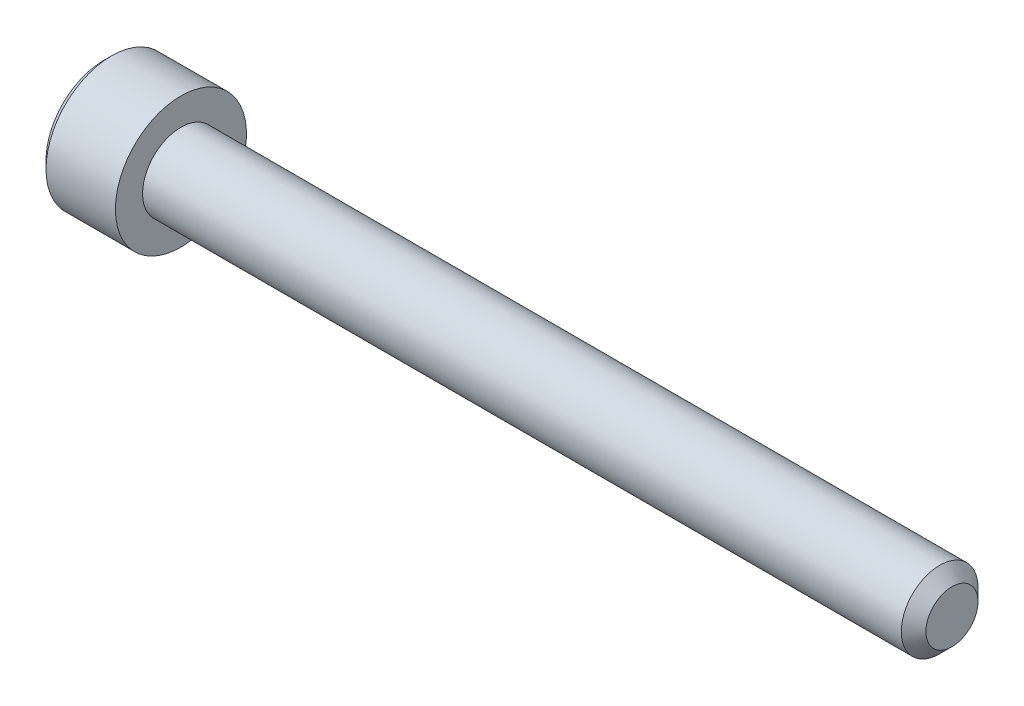
SolidWorks part; units mm, degrees
material "AISI Type 316L stainless steel"
ref_plane "Front Plane" through (0, 0, 0) normal (0, 0, 1) x (1, 0, 0)
ref_plane "Top Plane" through (0, 0, 0) normal (0, 1, 0) x (1, 0, 0)
ref_plane "Right Plane" through (0, 0, 0) normal (1, 0, 0) x (0, 0, -1)
sketch "Sketch1" plane through (0, 0, 0) normal (0, 0, 1) x (1, 0, 0)
  line L0 (-88.7055, 0) -> (96.9812, 0) construction
  line L1 (0, 0) -> (0, 4.25)
  line L2 (0, 4.25) -> (5, 4.25)
  line L4 (55, 0) -> (55, 2.488)
  line L5 (55, 2.488) -> (5, 2.488)
  line L6 (5, 2.488) -> (5, 4.25)
  line L7 (0, 0) -> (55, 0)
  dimension "D1" = 50
  dimension "D2" = 2.488
  dimension "D3" = 4.25
  dimension "D4" = 5
revolve "Revolve1" add sketch "Sketch1" angle 360 about L0
chamfer "Chamfer1" distance 0.8 angle 45 1 edges at (55, 0, 2.488)
chamfer "Chamfer2" distance 0.5 angle 45 1 edges at (0, 0, 4.25)
sketch "Sketch3" plane through (0, 0, 0) normal (1, 0, 0) x (0, 0, -1)
  line L1 (-2.3094, 0) -> (-1.1547, -2)
  line L2 (-1.1547, -2) -> (1.1547, -2)
  line L3 (1.1547, -2) -> (2.3094, 0)
  line L4 (2.3094, 0) -> (1.1547, 2)
  line L5 (1.1547, 2) -> (-1.1547, 2)
  line L6 (-1.1547, 2) -> (-2.3094, 0)
  circle A0 centre (0, 0) radius 2 construction
  dimension "D1" = 4
extrude "Cut-Extrude1" cut sketch "Sketch3" along normal blind 2.5
chamfer "Chamfer3" distance 0.4 angle 45 6 edges at (0, 2, 0) (0, 1, 1.7321) (0, -1, 1.7321) (0, -2, 0) (0, -1, -1.7321) (0, 1, -1.7321)
sketch "Sketch5" plane through (55, 0, 0) normal (1, 0, 0) x (0, 0, -1)
  circle A0 centre (0, 0) radius 2.488
  dimension "D1" = 4.976
curve "Helix/Spiral1" pitch 0.8 height 55 turns 68.75
sketch "Sketch8" plane through (0, 0, 0) normal (0, 1, 0) x (1, 0, 0)
  line L0 (55, 2.488) -> (55, 1.8816) construction
  line L1 (55.1, 2.0549) -> (55.5251, 2.7912)
  line L2 (55.5251, 2.7912) -> (54.4749, 2.7912)
  line L3 (54.4749, 2.7912) -> (54.9, 2.0549)
  line L4 (55, -1.688) -> (55, 1.688) construction
  circle A0 centre (55, 2.488) radius 0.3032 construction
  arc A1 (55.1, 2.0549) -> (54.9, 2.0549) centre (55, 2.1126) cw
  dimension "D2" = 0.1155
  dimension "D1" = 0.6064
sweep "Cut-Sweep1" [suppressed] cut profiles "Sketch8" path "Helix/Spiral1"
equation "\"length\"= 50"
equation "\"D1@Sketch1\"=\"length\""
